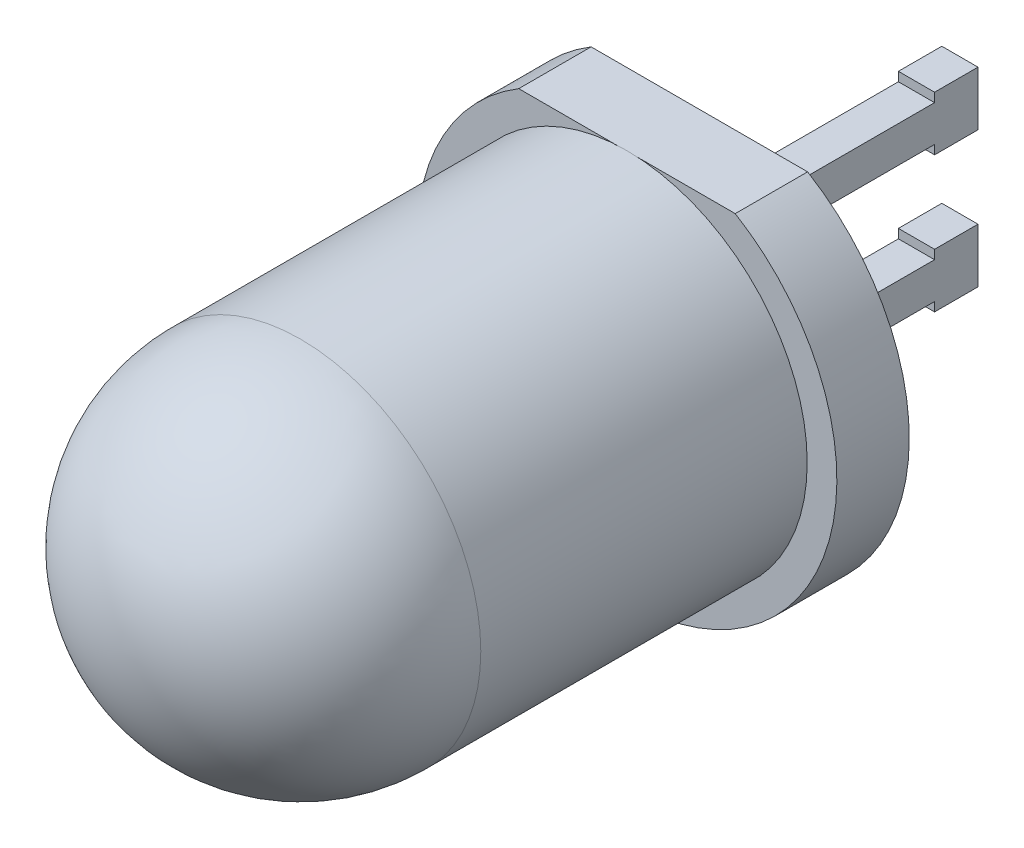
SolidWorks part; units mm, degrees
ref_plane "Front" through (0, 0, 0) normal (0, 0, 1) x (1, 0, 0)
ref_plane "Top" through (0, 0, 0) normal (0, 1, 0) x (1, 0, 0)
ref_plane "Right" through (0, 0, 0) normal (1, 0, 0) x (0, 0, -1)
sketch "Sketch1" plane through (0, 0, 0) normal (0, 0, 1) x (1, 0, 0)
  circle A0 centre (0, 0) radius 2.49
extrude "Extrude1" add sketch "Sketch1" along normal blind 7
fillet "Fillet2" radius 2.49 1 edges at (2.49, 0, 7)
sketch "Sketch2" plane through (0, 0, 0) normal (0, 0, -1) x (-1, 0, 0)
  circle A0 centre (0, 0) radius 2.9
extrude "Extrude2" add sketch "Sketch2" along normal blind 1
sketch "Sketch3" plane through (0, 0, -1) normal (0, 0, -1) x (-1, 0, 0)
  line L1 (1.7838, 3.0522) -> (-1.9807, 3.0522)
  line L2 (1.7838, 3.0522) -> (1.7838, 2.4846)
  line L3 (1.7838, 2.4846) -> (-1.9807, 2.4846)
  line L4 (-1.9807, 3.0522) -> (-1.9807, 2.4846)
extrude "Cut-Extrude3" cut sketch "Sketch3" against normal blind 1
sketch "Sketch5" plane through (0, 0, -1) normal (0, 0, -1) x (-1, 0, 0)
  line L0 (-0.25, -0.6897) -> (0.25, -0.6897)
  line L1 (-0.25, 1.1897) -> (0.25, 1.1897)
  line L2 (-0.25, 1.1897) -> (-0.25, 0.6897)
  line L3 (-0.25, 0.6897) -> (0.25, 0.6897)
  line L4 (0.25, 1.1897) -> (0.25, 0.6897)
  line L5 (-0.25, -0.6897) -> (-0.25, -1.1897)
  line L6 (-0.25, -1.1897) -> (0.25, -1.1897)
  line L7 (0.25, -0.6897) -> (0.25, -1.1897)
  line L8 (0, 3.0099) -> (0, -3.5406) construction
  line L9 (-3.7645, 0) -> (4.0017, 0) construction
  dimension "D1" = 0.5
  dimension "D2" = 0.5
  dimension "D3" = 1.3794
extrude "Extrusão1" add sketch "Sketch5" along normal blind 28 contours L5 L6 L7 L0
extrude "Extrusão2" add sketch "Sketch5<3>" along normal blind 25.4 contours L3 L4 L1 L2
sketch "Sketch5<3>" plane through (0, 0, -1) normal (0, 0, -1) x (-1, 0, 0) same geometry as "Sketch5"
sketch "Esboço1" plane through (-0.25, 0, 0) normal (-1, 0, 0) x (0, 0, 1)
  line L0 (-1, 1.1897) -> (-1, 0.6897) construction
  line L1 (-4, 1.3147) -> (-5.5, 1.3147)
  line L2 (-4, 1.3147) -> (-4, 0.5647)
  line L3 (-4, 0.5647) -> (-5.5, 0.5647)
  line L4 (-5.5, 1.3147) -> (-5.5, 0.5647)
  line L5 (-4, -0.5647) -> (-5.5, -0.5647)
  line L6 (-4, -0.5647) -> (-4, -1.3147)
  line L7 (-4, -1.3147) -> (-5.5, -1.3147)
  line L8 (-5.5, -0.5647) -> (-5.5, -1.3147)
  line L9 (-26.4, 0.6897) -> (-1, 0.6897) construction
  line L10 (-29, -0.6897) -> (-1, -0.6897) construction
  line L11 (-29, -1.1897) -> (-1, -1.1897) construction
  point P8 (-1, 0.9397)
  dimension "D1" = 3
  dimension "D2" = 0.75
  dimension "D3" = 0.125
  dimension "D4" = 1.5
  dimension "D5" = 0.125
  dimension "D6" = 0.125
extrude "Extrusão3" add sketch "Esboço1" against normal up to surface (0.5 mm away) up to face at (0.25, -0.9397, -15)
sketch "ｽｹｯﾁ1" plane through (0.25, 0, 0) normal (1, 0, 0) x (0, 0, -1)
  line L7 (4.6, -2.9) -> (29, -2.9)
  line L8 (4.6, -2.9) -> (4.6, 2.4846)
  line L9 (4.6, 2.4846) -> (29, 2.4846)
  line L10 (29, -2.9) -> (29, 2.4846)
extrude "ｶｯﾄ - 押し出し4" cut sketch "ｽｹｯﾁ1" against normal blind 10
sketch "ｽｹｯﾁ2" plane through (0, 0, -1) normal (0, 0, -1) x (-1, 0, 0)
  line L0 (-0.25, 1.1897) -> (0.25, 0.6897) construction
  line L1 (-0.25, -0.6897) -> (0.25, -1.1897) construction
  circle A0 centre (0, 0.9397) radius 0.3536
  circle A1 centre (0, -0.9397) radius 0.3536
